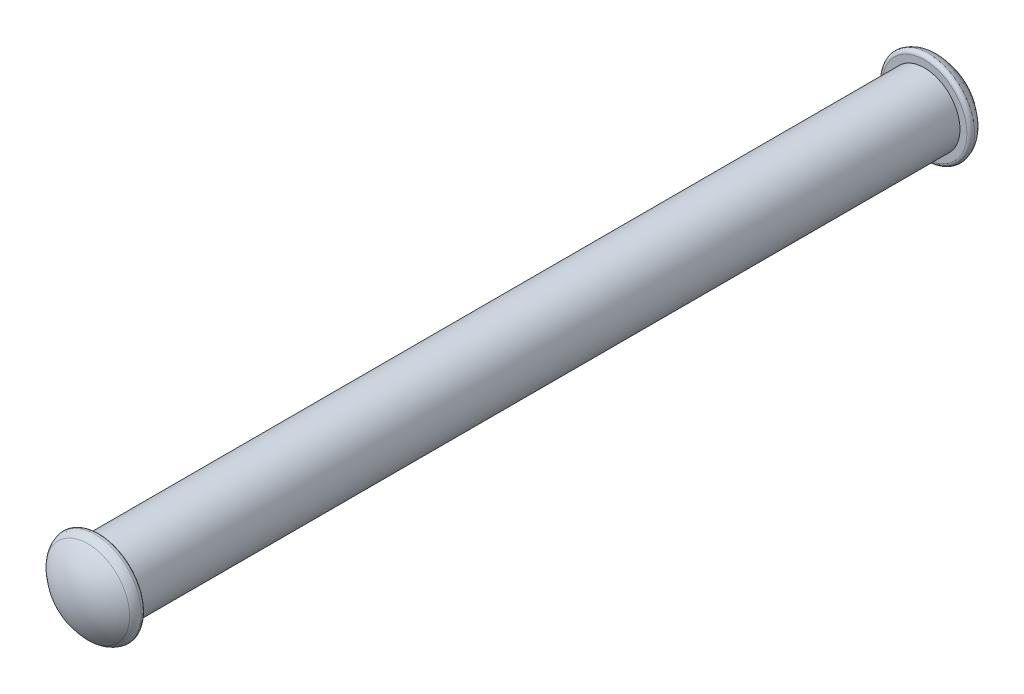
SolidWorks part; units mm, degrees
ref_plane "Front Plane" through (0, 0, 0) normal (0, 0, 1) x (1, 0, 0)
ref_plane "Top Plane" through (0, 0, 0) normal (0, 1, 0) x (1, 0, 0)
ref_plane "Right Plane" through (0, 0, 0) normal (1, 0, 0) x (0, 0, -1)
sketch "Sketch1" plane through (0, 0, 0) normal (0, 0, 1) x (1, 0, 0)
  circle A0 centre (0, 0) radius 0.5
  dimension "D1" = 1
extrude "Boss-Extrude1" add sketch "Sketch1" along normal mid plane 11.6
sketch "Sketch2" plane through (0, 0, 5.8) normal (0, 0, 1) x (1, 0, 0)
  circle A0 centre (0, 0) radius 0.65
  dimension "D1" = 1.3
extrude "Boss-Extrude2" add sketch "Sketch2" along normal blind 0.1
dome "Dome1" faces to dome 1 distance 0.3 reverse direction no elliptical dome no face at (0.65, 0, 5.9) parameters "D1"=0.3
fillet "Fillet1" radius 0.2 1 edges at (0.65, 0, 5.9)
fillet "Fillet3" radius 0.05 1 edges at (0.65, 0, 5.8)
mirror "Mirror2" about plane through (0, 0, 0) normal (0, 0, 1) of "Fillet3", "Dome1", "Fillet1", "Boss-Extrude2"
